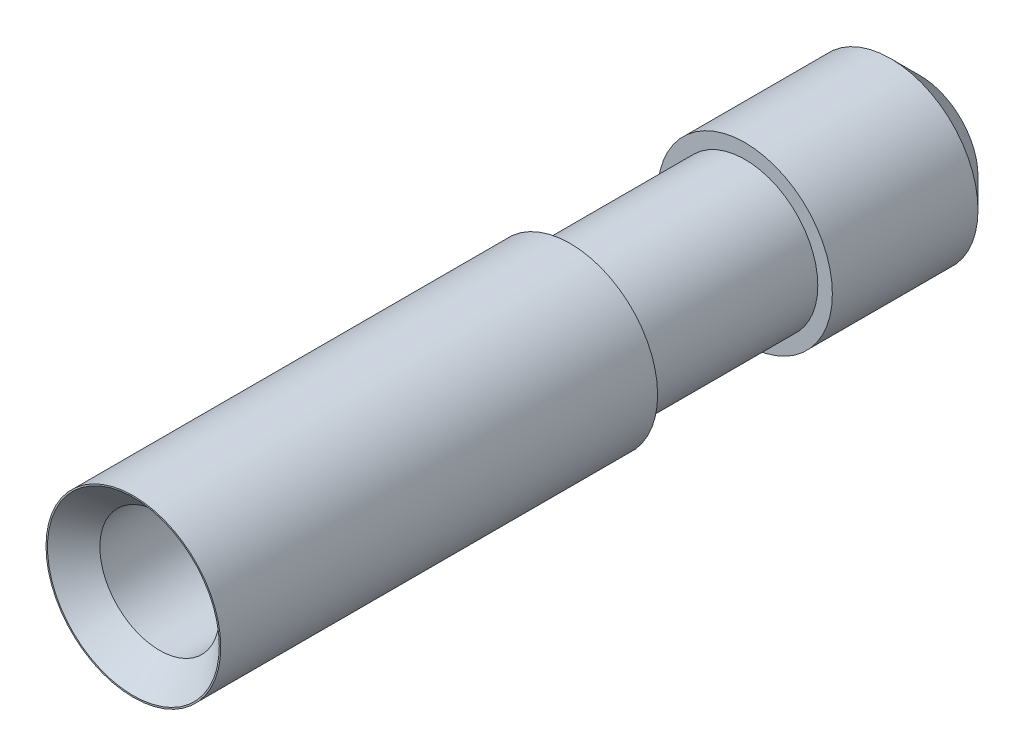
SolidWorks part; units mm, degrees
material "1.4000 (X6Cr13)"
ref_plane "Plan de face" through (0, 0, 0) normal (0, 0, 1) x (1, 0, 0)
ref_plane "Plan de dessus" through (0, 0, 0) normal (0, 1, 0) x (1, 0, 0)
ref_plane "Plan de droite" through (0, 0, 0) normal (1, 0, 0) x (0, 0, -1)
sketch "Esquisse1" plane through (0, 0, 0) normal (0, 0, 1) x (1, 0, 0)
  circle A0 centre (0, 0) radius 3
  dimension "D1" = 6
extrude "Boss.-Extru.1" add sketch "Esquisse1" along normal blind 27 contours A0
cosmetic thread "Représentation de filetage1" parameters "D1"=6, "D2"=4.891
sketch "Esquisse7" plane through (0, 0, 27) normal (0, 0, 1) x (1, 0, 0)
  circle A1 centre (0, 0) radius 2.05
  dimension "D1" = 4.1
hole_wizard "Diamètre du perçage Ø2.0 (2)1" positions "Esquisse5" profile "Esquisse4" hole size "Ø2.0" standard "ISO"
sketch "Esquisse5" plane through (0, 0, 0) normal (0, 0, -1) x (-1, 0, 0)
  point P0 (0, 0)
sketch "Esquisse4" plane through (0, 0, 0) normal (1, 0, 0) x (0, 1, 0)
  line L0 (0, 0) -> (0, 3)
  line L1 (0, 3) -> (1, 3)
  line L2 (1, 3) -> (1, 0)
  line L5 (1, 0) -> (0, 0)
  line L10 (0, 3) -> (-1, 3) construction
  line L11 (0, -6.35) -> (0, 107.95) construction
  dimension "Diamètre du perçage" = 2
  dimension "Profondeur du perçage" = 3
  dimension "Angle de pointe" = 180
sketch "Esquisse6" plane through (0, 0, 27) normal (0, 0, 1) x (1, 0, 0)
  line L1 (-6.0949, -5.2635) -> (5.6553, -5.2635)
  line L2 (-6.0949, -5.2635) -> (-6.0949, 6.1211)
  line L3 (-6.0949, 6.1211) -> (5.6553, 6.1211)
  line L4 (5.6553, -5.2635) -> (5.6553, 6.1211)
  circle A0 centre (0, 0) radius 2.5
  dimension "D1" = 5
extrude "Enlèv. mat.-Extru.1" cut sketch "Esquisse6" against normal blind 6 from offset 15 offset against normal yes
chamfer "Chanfrein1" distance 1 angle 45 1 edges at (3, 0, 0)
chamfer "Chanfrein2" [suppressed] distance 0.75 angle 45
hole_wizard "Diamètre du perçage Ø4.1 (4.1)1" positions "Esquisse9" profile "Esquisse8" hole size "Ø4.1" standard "ISO"
sketch "Esquisse9" plane through (0, 0, 27) normal (0, 0, 1) x (1, 0, 0)
  point P0 (0, 0)
sketch "Esquisse8" plane through (0, 0, 27) normal (1, 0, 0) x (0, -1, 0)
  line L0 (0, 0) -> (0, 24)
  line L1 (0, 24) -> (2.05, 24)
  line L2 (2.05, 24) -> (2.05, 0)
  line L5 (2.05, 0) -> (0, 0)
  line L10 (0, 24) -> (-2.05, 24) construction
  line L11 (0, -6.35) -> (0, 107.95) construction
  dimension "Diamètre du perçage" = 4.1
  dimension "Profondeur du perçage" = 24
  dimension "Angle de pointe" = 180
chamfer "Chanfrein3" distance 0.9 angle 45 1 edges at (2.05, 0, 27)
